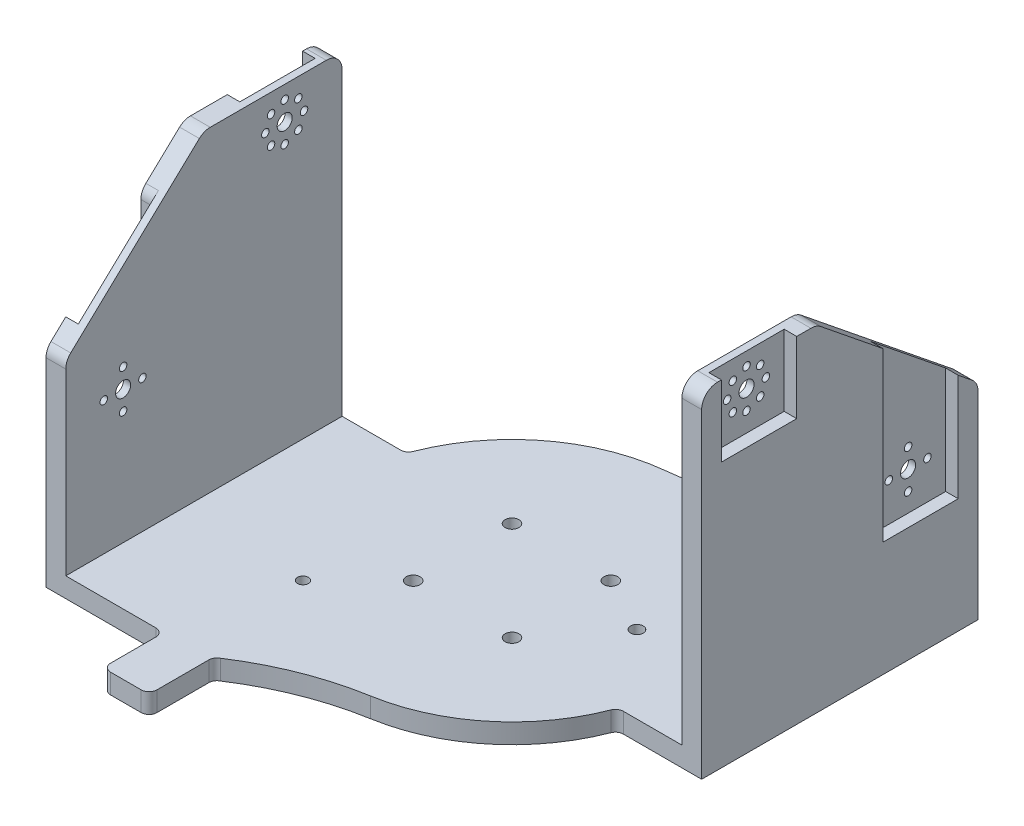
SolidWorks part; units mm, degrees
ref_plane "Front" through (0, 0, 0) normal (0, 0, 1) x (1, 0, 0)
ref_plane "Top" through (0, 0, 0) normal (0, 1, 0) x (1, 0, 0)
ref_plane "Right" through (0, 0, 0) normal (1, 0, 0) x (0, 0, -1)
sketch "Sketch2" plane through (0, 0, 0) normal (0, 1, 0) x (1, 0, 0)
  line L0 (0, 0) -> (0, -141.6255) construction
  line L1 (-115, -141.6255) -> (115, -141.6255)
  line L2 (-115, -141.6255) -> (-115, 141.6255)
  line L3 (-115, 141.6255) -> (115, 141.6255)
  line L4 (115, -141.6255) -> (115, 141.6255)
  line L5 (0, 0) -> (-115, 0) construction
  point P0 (0, 0)
  dimension "D1" = 283.251
  dimension "D2" = 230
extrude "Boss-Extrude1" add sketch "Sketch2" along normal blind 10
sketch "Sketch3" plane through (0, 0, 0) normal (0, 1, 0) x (1, 0, 0)
  line L0 (-115, -141.6255) -> (115, -141.6255) construction
  line L1 (-115, 141.6255) -> (-125, 141.6255)
  line L2 (-115, 141.6255) -> (-115, -141.6255)
  line L3 (-115, -141.6255) -> (-125, -141.6255)
  line L4 (-125, 141.6255) -> (-125, -141.6255)
  line L5 (0, 0) -> (0, 141.6255) construction
  line L6 (115, 141.6255) -> (-115, 141.6255) construction
  line L7 (125, 141.6255) -> (125, -141.6255)
  line L8 (115, -141.6255) -> (125, -141.6255)
  line L9 (115, 141.6255) -> (115, -141.6255)
  line L10 (115, 141.6255) -> (125, 141.6255)
  dimension "D1" = 10
extrude "Boss-Extrude2" add sketch "Sketch3" along normal blind 170
sketch "Sketch4" plane through (0, 10, 0) normal (0, 1, 0) x (1, 0, 0)
  point P4 (0, 0)
hole_wizard "M6 Clearance Hole1" positions "Sketch5" profile "Sketch6" hole size "M6" standard "ANSI Metric" end condition up to next
sketch "Sketch5" plane through (0, 10, 0) normal (0, 1, 0) x (1, 0, 0)
  line L0 (0, 0) -> (0, 25) construction
  line L1 (0, 25) -> (-25, 25) construction
  line L3 (0, 25) -> (25, 25) construction
  point P0 (-25, 25)
  point P13 (25, 25)
  point P14 (25, -25)
  point P15 (-25, -25)
  dimension "D1" = 25
  dimension "D2" = 4
sketch "Sketch6" plane through (-25, 10, -25) normal (1, 0, 0) x (0, 0, 1)
  line L0 (0, 0) -> (0, 10)
  line L1 (0, 10) -> (3.5, 10)
  line L2 (3.5, 10) -> (3.5, 0)
  line L5 (3.5, 0) -> (0, 0)
  line L11 (0, -6.35) -> (0, 107.95) construction
  dimension "Thru Hole Dia." = 7
  dimension "Thru Hole Depth" = 10
sketch "Sketch7" plane through (115, 0, 0) normal (-1, 0, 0) x (0, 0, 1)
  line L0 (-141.6255, 170) -> (141.6255, 170) construction
  line L1 (0, 153.49) -> (0, 163.269) construction
  line L2 (0, 153.49) -> (0, 163.269) construction
  circle A0 centre (0, 153.49) radius 3.81
  circle A1 centre (0, 163.269) radius 1.8987
  circle A2 centre (6.9148, 160.4048) radius 1.8987
  circle A3 centre (9.779, 153.49) radius 1.8987
  circle A4 centre (6.9148, 146.5752) radius 1.8987
  circle A5 centre (0, 143.711) radius 1.8987
  circle A6 centre (-6.9148, 146.5752) radius 1.8987
  circle A7 centre (-9.779, 153.49) radius 1.8987
  circle A8 centre (-6.9148, 160.4048) radius 1.8987
  point P7 (0, 170)
  dimension "D1" = 7.62
  dimension "D3" = 3.7973
  dimension "D2" = 16.51
  dimension "D6" = 9.779
  dimension "D5" = 8
extrude "Cut-Extrude1" cut sketch "Sketch7" against normal through all both and the other way through all
sketch "Sketch8" plane through (0, 170, 0) normal (0, 1, 0) x (1, 0, 0)
  line L1 (118.65, -19.05) -> (125, -19.05)
  line L2 (118.65, -19.05) -> (118.65, 19.05)
  line L3 (118.65, 19.05) -> (125, 19.05)
  line L4 (125, -19.05) -> (125, 19.05)
  line L5 (118.65, -19.05) -> (125, 19.05) construction
  line L6 (118.65, 19.05) -> (125, -19.05) construction
  line L9 (125, -141.6255) -> (125, 141.6255) construction
  line L10 (0, 0) -> (0, 141.6255) construction
  line L11 (115, 141.6255) -> (-115, 141.6255) construction
  line L13 (-118.65, 19.05) -> (-125, -19.05) construction
  line L14 (-118.65, -19.05) -> (-125, 19.05) construction
  line L16 (-125, -19.05) -> (-125, 19.05)
  line L17 (-118.65, 19.05) -> (-125, 19.05)
  line L18 (-118.65, -19.05) -> (-118.65, 19.05)
  line L19 (-118.65, -19.05) -> (-125, -19.05)
  point P0 (121.825, 0)
  point P12 (125, 0)
  point P23 (-121.825, 0)
  dimension "D1" = 38.1
  dimension "D2" = 6.35
extrude "Cut-Extrude2" cut sketch "Sketch8" against normal blind 36.025
sketch "Sketch9" plane through (125, 0, 0) normal (1, 0, 0) x (0, 0, -1)
  line L0 (65.2449, 60.526) -> (71.3409, 60.526) construction
  line L2 (100.7649, 96.554) -> (100.7649, 58.026)
  line L3 (100.7649, 58.026) -> (62.7449, 58.026)
  line L4 (62.7449, 96.554) -> (62.7449, 58.026)
  line L5 (100.7649, 96.554) -> (62.7449, 58.026) construction
  line L6 (100.7649, 58.026) -> (62.7449, 96.554) construction
  line L7 (65.2449, 69.67) -> (65.2449, 60.526) construction
  line L9 (62.7449, 96.554) -> (100.7649, 96.554) construction
  line L10 (62.7449, 96.554) -> (62.7449, 170)
  line L11 (19.05, 170) -> (141.6255, 170) construction
  line L12 (62.7449, 170) -> (100.7649, 170)
  line L13 (100.7649, 170) -> (100.7649, 96.554)
  point P0 (81.7549, 77.29)
  point P10 (81.7549, 87.069)
  point P11 (71.9759, 77.29)
  point P13 (81.7549, 67.511)
  point P15 (91.5339, 77.29)
  dimension "D1" = 2.5
  dimension "D2" = 2.5
extrude "Cut-Extrude3" cut sketch "Sketch9" against normal blind 6.35
sketch "Sketch11" plane through (118.65, 0, 0) normal (1, 0, 0) x (0, 0, -1)
  circle A0 centre (81.7549, 77.29) radius 3.81
  circle A1 centre (0, 153.49) radius 3.81 construction
extrude "Cut-Extrude4" cut sketch "Sketch11" against normal up to next
hole_wizard "#6 Clearance Hole1" positions "Sketch12" profile "Sketch13" hole size "#6" standard "ANSI Inch" end condition up to next
sketch "Sketch12" plane through (118.65, 0, 0) normal (1, 0, 0) x (0, 0, -1)
  point P0 (81.7549, 87.069)
  point P3 (71.9759, 77.29)
  point P6 (91.5339, 77.29)
  point P10 (81.7549, 67.511)
sketch "Sketch13" plane through (118.65, 87.069, -81.7549) normal (0, 1, 0) x (0, 0, -1)
  line L0 (0, 0) -> (0, 3.65)
  line L1 (0, 3.65) -> (1.8986, 3.65)
  line L2 (1.8986, 3.65) -> (1.8986, 0)
  line L5 (1.8986, 0) -> (0, 0)
  line L11 (0, -6.35) -> (0, 107.95) construction
  dimension "Thru Hole Dia." = 3.7973
  dimension "Thru Hole Depth" = 3.65
ref_plane "Plane1" through (0, 0, 0) normal (-0.7071, 0, 0.7071) x (0.7071, 0, 0.7071)
ref_axis "Axis1" through (0, 0, 0) along (0, 1, 0)
pattern_circular "CirPattern1" count 2 over 360 about axis through (0, 0, 0) along (0, 1, 0) of "Cut-Extrude3", "Cut-Extrude4", "#6 Clearance Hole1"
sketch "Esquisse1" plane through (0, 10, 0) normal (0, 1, 0) x (1, 0, 0)
  circle A0 centre (53, 110.7393) radius 3.175
  circle A1 centre (53, 10.2032) radius 3.175
  dimension "D1" = 6.35
  dimension "D2" = 6.35
extrude "Enlèv. mat.-Extru.1" cut sketch "Esquisse1" against normal up to next
sketch "Sketch17" plane through (0, 10, 0) normal (0, 1, 0) x (1, 0, 0)
  point P0 (-53, -52.7704)
  point P1 (-53, -153.3066)
hole_wizard "CBORE for M5 SHCS1" positions "Sketch18" profile "Sketch19" counterbore size "M5" standard "ANSI Metric" end condition through all
sketch "Sketch18" plane through (0, 0, 0) normal (0, -1, 0) x (-1, 0, 0)
  point P0 (53, -52.7704)
  point P3 (53, -153.3066)
sketch "Sketch19" plane through (-53, 0, 52.7704) normal (1, 0, 0) x (0, 0, -1)
  line L0 (0, 0) -> (0, 170)
  line L1 (0, 170) -> (2.75, 170)
  line L3 (2.75, 170) -> (2.75, 5)
  line L4 (2.75, 5) -> (5, 5)
  line L5 (5, 5) -> (5, 0)
  line L7 (5, 0) -> (0, 0)
  line L11 (0, -6.35) -> (0, 107.95) construction
  dimension "Thru Hole Dia." = 5.5
  dimension "Thru Hole Depth" = 170
  dimension "C'Bore Dia." = 10
  dimension "C'Bore Depth" = 5
sketch "Sketch15" plane through (0, 10, 0) normal (0, 1, 0) x (1, 0, 0)
  line L17 (115, 141.6255) -> (-115, 141.6255) construction
  line L23 (125, 141.6255) -> (-125, 141.6255)
  line L24 (-125, 141.6255) -> (-125, 29.05)
  line L25 (-125, 141.6255) -> (-125, 19.05) construction
  line L33 (-125, 29.05) -> (-82.5806, 29.05)
  line L34 (39.825, 123.9143) -> (66.175, 123.9143)
  line L36 (66.175, 123.9143) -> (66.175, 110.7649)
  line L39 (66.175, 110.7649) -> (125, 110.7649)
  line L42 (125, 110.7649) -> (125, 141.6255)
  line L45 (118.65, 100.7649) -> (125, 100.7649) construction
  line L46 (39.825, 77.9578) -> (39.825, 123.9143)
  line L48 (125, -141.6255) -> (125, -29.05)
  line L49 (125, -29.05) -> (82.5806, -29.05)
  line L52 (-66.175, -110.7649) -> (-125, -110.7649)
  line L53 (-125, -110.7649) -> (-125, -141.6255)
  line L56 (-66.175, -110.7649) -> (-66.175, -141.6255)
  line L57 (-39.825, -123.9143) -> (-66.175, -123.9143) [skipped]
  line L58 (-39.825, -77.9578) -> (-39.825, -123.9143) [skipped]
  line L59 (-66.175, -123.9143) -> (-66.175, -110.7649) [skipped]
  line L60 (-39.825, -77.9578) -> (-39.825, -141.6255)
  line L61 (-125, -141.6255) -> (125, -141.6255) [skipped]
  line L62 (-115, -141.6255) -> (115, -141.6255) construction
  line L63 (-39.825, -141.6255) -> (125, -141.6255)
  line L64 (-66.175, -141.6255) -> (-125, -141.6255)
  circle A0 centre (0, 0) radius 87.5412 construction
  circle A1 centre (-53, -52.7704) radius 2.75 construction
  circle A2 centre (53, 110.7393) radius 3.175 construction
  arc A3 (-82.5806, 29.05) -> (39.825, 77.9578) centre (0, 0) cw
  arc A5 (82.5806, -29.05) -> (-39.825, -77.9578) centre (0, 0) cw
  point P34 (0, 0)
  dimension "D1" = 10
  dimension "D3" = 10
  dimension "D4" = 10
  dimension "D5" = 10
  dimension "D2" = 10
  dimension "D6" = 10
  dimension "D7" = 2
extrude "Cut-Extrude5" cut sketch "Sketch15" against normal through all both and the other way through all
sketch "Sketch20" plane through (0, 10, 0) normal (0, 1, 0) x (1, 0, 0)
  line L0 (-65.41, -110.7649) -> (-66.175, -110.7649)
  line L1 (-65.41, -142.0082) -> (-65.41, -108.4765) construction
  line L2 (-65.41, -110.7649) -> (-65.41, -141.6255)
  line L3 (-65.41, -141.6255) -> (-66.175, -141.6255)
  line L4 (-66.175, -141.6255) -> (-66.175, -110.7649)
  line L7 (-66.175, -141.6255) -> (-39.825, -141.6255) construction
  line L8 (-39.825, -141.6255) -> (-39.825, -107.7487)
  line L9 (-39.825, -141.6255) -> (-39.825, -77.9578) construction
  line L10 (-41.9959, -111.306) -> (-41.9959, -141.6255)
  line L11 (39.825, 123.9143) -> (66.175, 123.9143)
  line L13 (-41.9959, -141.6255) -> (-39.825, -141.6255)
  line L14 (66.175, 123.9143) -> (39.825, 123.9143) construction
  line L16 (39.825, 123.9143) -> (39.825, 77.9578) construction
  line L17 (39.825, 101.0244) -> (39.825, 123.9143)
  line L18 (66.175, 123.9143) -> (66.175, 110.7649)
  line L19 (66.175, 110.7649) -> (65.41, 110.7649)
  line L23 (42, 104.5839) -> (42, 116.5839)
  line L24 (46, 120.5839) -> (61.41, 120.5839)
  line L25 (65.41, 116.5839) -> (65.41, 110.7649)
  arc A2 (-37.9959, -107.306) -> (-41.9959, -111.306) centre (-37.9959, -111.306) ccw construction
  arc A3 (-41.9959, -111.306) -> (-39.825, -107.7487) centre (-37.9959, -111.306) cw
  arc A6 (42, 104.5839) -> (39.825, 101.0244) centre (38, 104.5839) cw
  arc A7 (38, 100.5839) -> (42, 104.5839) centre (38, 104.5839) ccw construction
  arc A8 (42, 116.5839) -> (46, 120.5839) centre (46, 116.5839) cw
  arc A9 (61.41, 120.5839) -> (65.41, 116.5839) centre (61.41, 116.5839) cw
extrude "Cut-Extrude7" cut sketch "Sketch20" against normal through all both and the other way through all
fillet "Fillet2" radius 4 2 edges at (-41.9959, 5, 141.6255) (-65.41, 5, 141.6255)
fillet "Fillet3" radius 144 2 edges at (39.825, 5, -77.9578) (-39.825, 5, 77.9578)
fillet "Fillet4" radius 4 4 edges at (65.41, 5, -110.7649) (-82.5806, 5, -29.05) (82.5806, 5, 29.05) (-65.41, 5, 110.7649)
sketch "Sketch22" plane through (-125, 0, 0) normal (-1, 0, 0) x (0, 0, 1)
  line L0 (40.8574, 170) -> (110.7649, 104.051)
  line L1 (19.05, 170) -> (62.7449, 170) construction
  line L2 (110.7649, 0) -> (110.7649, 170) construction
  line L3 (100.7649, 94.051) -> (110.7649, 94.051) construction
  line L4 (110.7649, 94.051) -> (110.7649, 104.051) construction
  line L5 (19.05, 170) -> (40.8574, 170) construction
  line L6 (-19.05, 170) -> (-40.8574, 170) construction
  line L7 (-110.7649, 170) -> (29.05, 170) construction
  line L8 (40.8574, 170) -> (110.7649, 170)
  line L9 (110.7649, 170) -> (110.7649, 104.051)
  line L10 (19.05, 133.975) -> (19.05, 170) construction
  line L11 (100.7649, 58.026) -> (100.7649, 94.051) construction
extrude "Cut-Extrude8" cut sketch "Sketch22" against normal up to next
sketch "Sketch23" plane through (125, 0, 0) normal (1, 0, 0) x (0, 0, -1)
  line L0 (19.05, 170) -> (29.05, 170) construction
  line L1 (19.05, 170) -> (62.7449, 170) construction
  line L2 (29.05, 170) -> (110.7649, 104.051)
  line L3 (110.7649, 0) -> (110.7649, 170) construction
  line L4 (110.7649, 104.051) -> (110.7649, 94.051) construction
  line L5 (110.7649, 94.051) -> (100.7649, 94.051) construction
  line L6 (-19.05, 170) -> (-29.05, 170) construction
  line L7 (110.7649, 104.051) -> (110.7649, 170)
  line L8 (110.7649, 170) -> (29.05, 170)
  line L9 (100.7649, 58.026) -> (100.7649, 94.051) construction
  line L10 (19.05, 133.975) -> (19.05, 170) construction
extrude "Cut-Extrude9" cut sketch "Sketch23" against normal up to next
fillet "Fillet5" radius 8 6 edges at (120, 104.051, -110.7649) (120, 170, -29.05) (-120, 170, -29.05) (120, 170, 29.05) (-120, 170, 40.8574) (-120, 104.051, 110.7649)
split "Split1" [suppressed] bodies to split 136
fillet "Fillet6" radius 8 1 edges at (-121.825, 149.3519, 62.7449)
fillet "Fillet7" [suppressed] radius 10
equation "\"Longueur\"= 230"
equation "\"D2@Sketch2\"=\"Longueur\""
equation "\"Largeur\"= 280 + 2 * 1.6255mm"
equation "\"D1@Sketch2\"=\"Largeur\""
equation "\"D1@Sketch9\"=\"D2@Sketch9\""
